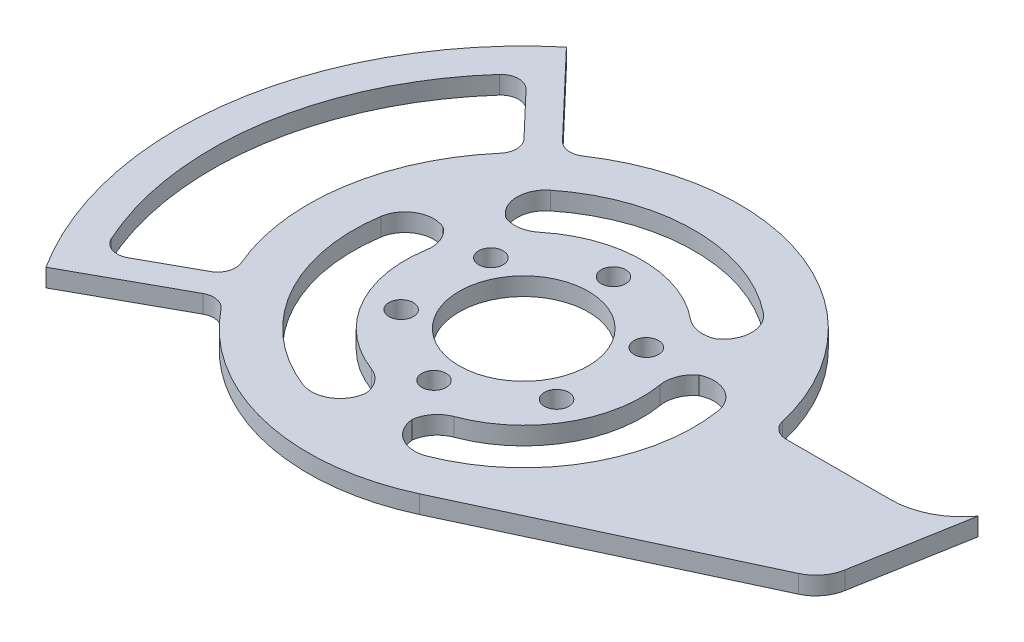
SolidWorks part; units mm, degrees
ref_plane "Front Plane" through (0, 0, 0) normal (0, 0, 1) x (1, 0, 0)
ref_plane "Top Plane" through (0, 0, 0) normal (0, 1, 0) x (1, 0, 0)
ref_plane "Right Plane" through (0, 0, 0) normal (1, 0, 0) x (0, 0, -1)
other "Center of Mass"
other "Bounding Box"
ref_plane "Default Plane" through (-8.9266, -12.7485, 0) normal (-0.1736, 0.9848, 0) x (0.9848, 0.1736, 0)
sketch "Sketch1" plane through (0, 0, 0) normal (0, 1, 0) x (1, 0, 0)
  line B0 (31.1591, 5.9433) -> (29.0547, 5.5565)
  line B1 (26.0289, -14.0552) -> (27.9189, -15.0583)
  line B2 (27.7728, 4.2372) -> (25.2042, -12.4109)
  line B3 (-45.8426, -24.1464) -> (-36.4371, -18.9694)
  line B4 (-29.0253, 29.0694) -> (-36.4331, 36.8405)
  line B5 (52.9152, -8.1642) -> (47.6562, -0.9862)
  line B6 (45.7373, -13.4232) -> (52.9152, -8.1642)
  line B7 (-2.3359, -29.5358) -> (-2.3709, -28.5547)
  line B8 (-6.3457, -27.9414) -> (-6.6748, -28.8663)
  line B9 (-22.2418, -12.44) -> (-7.3488, -24.4018)
  line B10 (-26.7467, -12.7449) -> (-25.9145, -12.2241)
  line B11 (-27.3708, -8.4752) -> (-28.3364, -8.6526)
  line B12 (-21.8942, 13.042) -> (-24.807, -5.8366)
  line B13 (-24.4107, 16.7909) -> (-23.5436, 16.3306)
  line B14 (-21.0251, 19.4663) -> (-21.6616, 20.2137)
  line B15 (0.3476, 25.482) -> (-17.4581, 18.5652)
  line B16 (2.3359, 29.5358) -> (2.3709, 28.5547)
  line B17 (6.3457, 27.9414) -> (6.6748, 28.8663)
  line B18 (22.2418, 12.44) -> (7.3488, 24.4018)
  line B19 (26.7467, 12.7449) -> (25.9145, 12.2241)
  line B20 (27.3708, 8.4752) -> (28.3364, 8.6526)
  line B21 (21.8942, -13.042) -> (24.807, 5.8366)
  line B22 (24.4107, -16.7909) -> (23.5436, -16.3306)
  line B23 (21.0251, -19.4663) -> (21.6616, -20.2137)
  line B24 (-0.3476, -25.482) -> (17.4581, -18.5652)
  line B25 (20.7267, -24.0129) -> (19.3394, -22.3839)
  line B26 (0.8423, -29.5693) -> (0.9185, -31.7076)
  line B27 (17.5559, -21.9333) -> (1.8539, -28.0329)
  line B28 (10.4325, 29.9563) -> (9.7153, 27.9404)
  line B29 (25.1866, 15.5141) -> (27.0003, 16.6493)
  line B30 (10.2168, 26.1705) -> (23.3502, 15.622)
  line B31 (-10.4325, -29.9563) -> (-9.7153, -27.9404)
  line B32 (-25.1866, -15.5141) -> (-27.0003, -16.6493)
  line B33 (-10.2168, -26.1705) -> (-23.3502, -15.622)
  line B34 (-0.8423, 29.5693) -> (-0.9185, 31.7076)
  line B35 (-17.5559, 21.9333) -> (-1.8539, 28.0329)
  line B36 (-20.7267, 24.0129) -> (-19.3394, 22.3839)
  line B37 (-31.1591, -5.9433) -> (-29.0547, -5.5565)
  line B38 (-26.0289, 14.0552) -> (-27.9189, 15.0583)
  line B39 (-27.7728, -4.2372) -> (-25.2042, 12.4109)
  line B40 (-25.2564, 32.1101) -> (-39.3478, 46.8924)
  line B41 (-51.6515, -32.8524) -> (-33.7603, -23.0048)
  line B42 (16.1018, -34.5303) -> (61.8073, -13.2175)
  line B43 (65.3772, -8.5651) -> (68.9058, 11.4462)
  line B44 (58.6548, 6.2434) -> (40.1861, 6.2434)
  arc B45 (42.6375, -6.5784) -> (45.7373, -13.4232) centre (43.4684, -10.3264) ccw
  arc B46 (33.0185, 4.6011) -> (31.1591, 5.9433) centre (31.4462, 4.382) ccw
  arc B47 (30.0963, -14.3389) -> (33.0185, 4.6011) centre (0, 0) ccw
  arc B48 (27.9189, -15.0583) -> (30.0963, -14.3389) centre (28.6631, -13.6561) ccw
  arc B49 (25.2042, -12.4109) -> (26.0289, -14.0552) centre (26.7731, -12.653) ccw
  arc B50 (29.0547, 5.5565) -> (27.7728, 4.2372) centre (29.3417, 3.9952) ccw
  arc B51 (47.6562, -0.9862) -> (42.6375, -6.5784) centre (44.5594, -3.2551) ccw
  arc B52 (-0.3476, -25.482) -> (-2.3709, -28.5547) centre (0.8021, -28.4415) ccw
  arc B53 (-6.6748, -28.8663) -> (-2.3359, -29.5358) centre (-4.5693, -29.6154) ccw
  arc B54 (-6.3457, -27.9414) -> (-7.3488, -24.4018) centre (-9.337, -26.8772) ccw
  arc B55 (-22.2418, -12.44) -> (-25.9145, -12.2241) centre (-24.2301, -14.9154) ccw
  arc B56 (-28.3364, -8.6526) -> (-26.7467, -12.7449) centre (-27.9323, -10.8506) ccw
  arc B57 (-27.3708, -8.4752) -> (-24.807, -5.8366) centre (-27.9448, -5.3525) ccw
  arc B58 (-21.8942, 13.042) -> (-23.5436, 16.3306) centre (-25.0321, 13.5262) ccw
  arc B59 (-21.6616, 20.2137) -> (-24.4107, 16.7909) centre (-23.363, 18.7648) ccw
  arc B60 (-21.0251, 19.4663) -> (-17.4581, 18.5652) centre (-18.6078, 21.5247) ccw
  arc B61 (0.3476, 25.482) -> (2.3709, 28.5547) centre (-0.8021, 28.4415) ccw
  arc B62 (6.6748, 28.8663) -> (2.3359, 29.5358) centre (4.5693, 29.6154) ccw
  arc B63 (6.3457, 27.9414) -> (7.3488, 24.4018) centre (9.337, 26.8772) ccw
  arc B64 (22.2418, 12.44) -> (25.9145, 12.2241) centre (24.2301, 14.9154) ccw
  arc B65 (28.3364, 8.6526) -> (26.7467, 12.7449) centre (27.9323, 10.8506) ccw
  arc B66 (27.3708, 8.4752) -> (24.807, 5.8366) centre (27.9448, 5.3525) ccw
  arc B67 (21.8942, -13.042) -> (23.5436, -16.3306) centre (25.0321, -13.5262) ccw
  arc B68 (21.6616, -20.2137) -> (24.4107, -16.7909) centre (23.363, -18.7648) ccw
  arc B69 (21.0251, -19.4663) -> (17.4581, -18.5652) centre (18.6078, -21.5247) ccw
  arc B70 (-28.914, 24.8111) -> (-35.0475, -14.9427) centre (0, 0) ccw
  arc B71 (-36.4371, -18.9694) -> (-35.0475, -14.9427) centre (-37.9681, -16.1879) ccw
  arc B72 (-50.2679, -22.6701) -> (-45.8426, -24.1464) centre (-47.3736, -21.3649) ccw
  arc B73 (-41.0975, 36.7667) -> (-50.2679, -22.6701) centre (0, 0) ccw
  arc B74 (-36.4331, 36.8405) -> (-41.0975, 36.7667) centre (-38.7312, 34.6498) ccw
  arc B75 (-28.914, 24.8111) -> (-29.0253, 29.0694) centre (-31.3235, 26.8787) ccw
  arc B76 (20.4939, -26.2943) -> (20.7267, -24.0129) centre (19.518, -25.0422) ccw
  arc B77 (2.6303, -33.2336) -> (20.4939, -26.2943) centre (0, 0) ccw
  arc B78 (0.9185, -31.7076) -> (2.6303, -33.2336) centre (2.505, -31.651) ccw
  arc B79 (1.8539, -28.0329) -> (0.8423, -29.5693) centre (2.4288, -29.5127) ccw
  arc B80 (19.3394, -22.3839) -> (17.5559, -21.9333) centre (18.1308, -23.4131) ccw
  arc B81 (12.5246, 30.8954) -> (10.4325, 29.9563) centre (11.9282, 29.4242) ccw
  arc B82 (27.466, 18.8947) -> (12.5246, 30.8954) centre (0, 0) ccw
  arc B83 (27.0003, 16.6493) -> (27.466, 18.8947) centre (26.1581, 17.9949) ccw
  arc B84 (23.3502, 15.622) -> (25.1866, 15.5141) centre (24.3444, 16.8597) ccw
  arc B85 (9.7153, 27.9404) -> (10.2168, 26.1705) centre (11.211, 27.4082) ccw
  arc B86 (-12.5246, -30.8954) -> (-10.4325, -29.9563) centre (-11.9282, -29.4242) ccw
  arc B87 (-27.466, -18.8947) -> (-12.5246, -30.8954) centre (0, 0) ccw
  arc B88 (-27.0003, -16.6493) -> (-27.466, -18.8947) centre (-26.1581, -17.9949) ccw
  arc B89 (-23.3502, -15.622) -> (-25.1866, -15.5141) centre (-24.3444, -16.8597) ccw
  arc B90 (-9.7153, -27.9404) -> (-10.2168, -26.1705) centre (-11.211, -27.4082) ccw
  arc B91 (-2.6303, 33.2336) -> (-20.4939, 26.2943) centre (0, 0) ccw
  arc B92 (-0.9185, 31.7076) -> (-2.6303, 33.2336) centre (-2.505, 31.651) ccw
  arc B93 (-1.8539, 28.0329) -> (-0.8423, 29.5693) centre (-2.4288, 29.5127) ccw
  arc B94 (-19.3394, 22.3839) -> (-17.5559, 21.9333) centre (-18.1308, 23.4131) ccw
  arc B95 (-20.4939, 26.2943) -> (-20.7267, 24.0129) centre (-19.518, 25.0422) ccw
  arc B96 (-33.0185, -4.6011) -> (-31.1591, -5.9433) centre (-31.4462, -4.382) ccw
  arc B97 (-30.0963, 14.3389) -> (-33.0185, -4.6011) centre (0, 0) ccw
  arc B98 (-27.9189, 15.0583) -> (-30.0963, 14.3389) centre (-28.6631, 13.6561) ccw
  arc B99 (-25.2042, 12.4109) -> (-26.0289, 14.0552) centre (-26.7731, 12.653) ccw
  arc B100 (-29.0547, -5.5565) -> (-27.7728, -4.2372) centre (-29.3417, -3.9952) ccw
  arc B101 (-39.3478, 46.8924) -> (-51.6515, -32.8524) centre (0, 0) ccw
  arc B102 (-29.7495, -23.8029) -> (-33.7603, -23.0048) centre (-32.2291, -25.7868) ccw
  arc B103 (-29.7495, -23.8029) -> (16.1018, -34.5303) centre (0, 0) ccw
  arc B104 (61.8073, -13.2175) -> (65.3772, -8.5651) centre (59.1237, -7.4624) ccw
  arc B105 (58.6548, 6.2434) -> (68.9058, 11.4462) centre (58.6548, 18.9434) ccw
  arc B106 (37.0948, 8.6939) -> (40.1861, 6.2434) centre (40.1861, 9.4184) ccw
  arc B107 (37.0948, 8.6939) -> (-21.1923, 31.6622) centre (0, 0) ccw
  arc B108 (-25.2564, 32.1101) -> (-21.1923, 31.6622) centre (-22.9583, 34.3008) ccw
sketch_block_instance "Wepon-1"
sketch_block "Wepon"
extrude "Boss-Extrude1" add sketch "Sketch1" along normal blind 3.175
sketch "Sketch2" plane through (0, 3.175, 0) normal (0, 1, 0) x (1, 0, 0)
  line L0 (45.7373, -13.4232) -> (52.9152, -8.1642)
  line L1 (52.9152, -8.1642) -> (47.6562, -0.9862)
  circle A0 centre (0, 0) radius 38.1
  arc A1 (42.6375, -6.5784) -> (45.7373, -13.4232) centre (43.4684, -10.3264) ccw
  arc A2 (42.6375, -6.5784) -> (47.6562, -0.9862) centre (44.5594, -3.2551) cw
extrude "Boss-Extrude2" add sketch "Sketch2" against normal up to surface (3.175 mm away) up to face at (-28.9513, 0, -4.4668)
sketch "Sketch5" plane through (0, 3.175, 0) normal (0, 1, 0) x (1, 0, 0)
  arc B0 (-18.8515, 23.5457) -> (18.8515, 23.5457) centre (0, 0) cw
  arc B1 (18.8515, 23.5457) -> (18.5756, 15.4086) centre (15.6765, 19.5801) cw
  arc B2 (18.5756, 15.4086) -> (13.3403, 16.1601) centre (16.5743, 20.0777) cw
  arc B3 (13.3403, 16.1601) -> (-13.3403, 16.1601) centre (0, 0) ccw
  arc B4 (-13.3403, 16.1601) -> (-18.5756, 15.4086) centre (-16.5743, 20.0777) cw
  arc B5 (-18.5756, 15.4086) -> (-18.8515, 23.5457) centre (-15.6765, 19.5801) cw
  arc B6 (-20.6652, 3.473) -> (-22.632, 8.3827) centre (-25.6749, 4.3149) ccw
  arc B7 (-22.632, 8.3827) -> (-29.8169, 4.553) centre (-24.7951, 3.7862) ccw
  arc B8 (-29.8169, 4.553) -> (-10.9654, -28.0987) centre (0, 0) ccw
  arc B9 (-10.9654, -28.0987) -> (-4.0564, -23.7912) centre (-9.1186, -23.3663) ccw
  arc B10 (-4.0564, -23.7912) -> (-7.3249, -19.6331) centre (-9.1007, -24.3926) ccw
  arc B11 (-7.3249, -19.6331) -> (-20.6652, 3.473) centre (0, 0) cw
  arc B12 (7.3249, -19.6331) -> (4.0564, -23.7912) centre (9.1007, -24.3926) ccw
  arc B13 (4.0564, -23.7912) -> (10.9654, -28.0987) centre (9.1186, -23.3663) ccw
  arc B14 (10.9654, -28.0987) -> (29.8169, 4.553) centre (0, 0) ccw
  arc B15 (29.8169, 4.553) -> (22.632, 8.3827) centre (24.7951, 3.7862) ccw
  arc B16 (22.632, 8.3827) -> (20.6652, 3.473) centre (25.6749, 4.3149) ccw
  arc B17 (20.6652, 3.473) -> (7.3249, -19.6331) centre (0, 0) cw
  circle B18 centre (0, 0) radius 11.43
  circle B19 centre (13.7482, 7.9375) radius 2.159
  circle B20 centre (0, 15.875) radius 2.159
  circle B21 centre (-13.7482, 7.9375) radius 2.159
  circle B22 centre (-13.7482, -7.9375) radius 2.159
  circle B23 centre (0, -15.875) radius 2.159
  circle B24 centre (13.7482, -7.9375) radius 2.159
sketch_block_instance "Wepon for Pulley-1"
sketch_block "Wepon for Pulley"
extrude "Cut-Extrude2" cut sketch "Sketch5" against normal through all both and the other way through all
